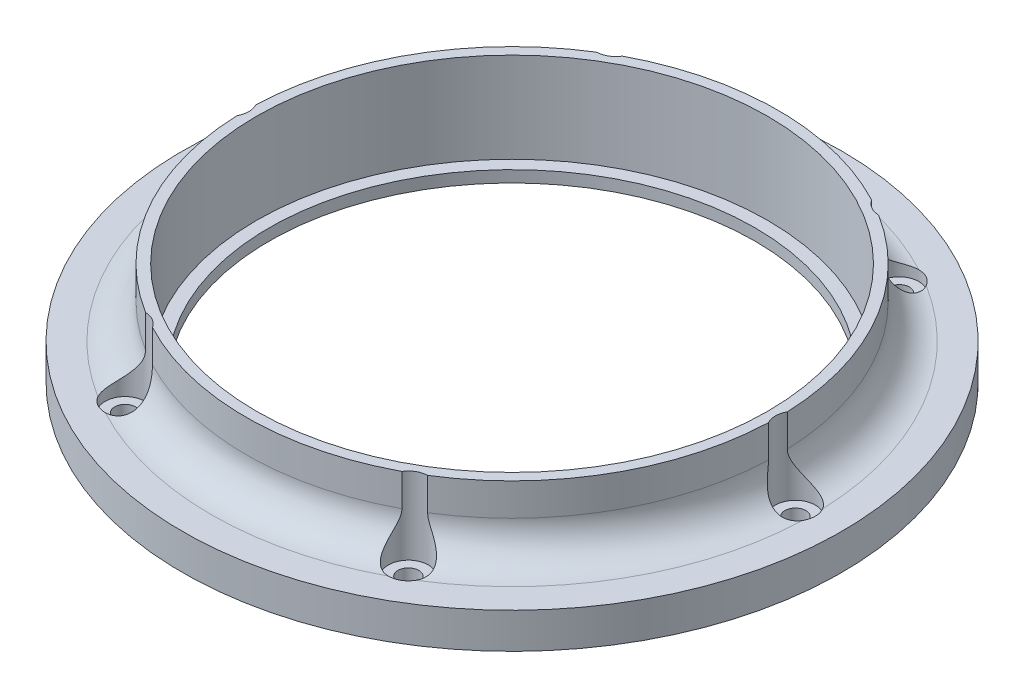
SolidWorks part; units mm, degrees
ref_plane "Front Plane" through (0, 0, 0) normal (0, 0, 1) x (1, 0, 0)
ref_plane "Top Plane" through (0, 0, 0) normal (0, 1, 0) x (1, 0, 0)
ref_plane "Right Plane" through (0, 0, 0) normal (1, 0, 0) x (0, 0, -1)
sketch "Sketch1" plane through (0, 0, 0) normal (0, 1, 0) x (1, 0, 0)
  circle A0 centre (0, 0) radius 61.25 construction
  circle A1 centre (0, 0) radius 55.25
  circle A2 centre (0, 0) radius 57.5
  dimension "D1" = 122.5
  dimension "D2" = 110.5
  dimension "D3" = 115
extrude "Boss-Extrude1" add sketch "Sketch1" along normal blind 22
sketch "Sketch2" plane through (0, 0, 0) normal (0, -1, 0) x (1, 0, 0)
  circle A0 centre (0, 0) radius 61.25 construction
  circle A1 centre (0, 0) radius 71.25
  circle A2 centre (0, 0) radius 57.5 construction
  circle A3 centre (0, 0) radius 57.5
  dimension "D1" = 122.5
  dimension "D2" = 10
extrude "Boss-Extrude2" add sketch "Sketch2" against normal blind 7.5
hole_wizard "CBORE for M4 SBHCS1" positions "Sketch6" profile "Sketch5" counterbore size "M4" standard "ANSI Metric" end condition through all
sketch "Sketch6" plane through (0, 7.5, 0) normal (0, 1, 0) x (1, 0, 0)
  circle A0 centre (0, 0) radius 61.25 construction
  point P0 (-61.25, 0)
  dimension "D1" = 122.5
sketch "Sketch5" plane through (-61.25, 7.5, 0) normal (1, 0, 0) x (0, 0, 1)
  line L0 (0, 0) -> (0, 7.5)
  line L1 (0, 7.5) -> (2.25, 7.5)
  line L3 (2.25, 7.5) -> (2.25, 2.2)
  line L4 (2.25, 2.2) -> (4.3, 2.2)
  line L5 (4.3, 2.2) -> (4.3, 0)
  line L7 (4.3, 0) -> (0, 0)
  line L11 (0, -6.35) -> (0, 107.95) construction
  dimension "Thru Hole Dia." = 4.5
  dimension "Thru Hole Depth" = 7.5
  dimension "C'Bore Dia." = 8.6
  dimension "C'Bore Depth" = 2.2
fillet "Fillet2" radius 7.5 1 edges at (57.5, 7.5, 0)
sketch "Sketch7" plane through (0, 7.5, 0) normal (0, 1, 0) x (1, 0, 0)
  circle A1 centre (-61.25, 0) radius 4.3
  circle A2 centre (-61.25, 0) radius 4.3
  dimension "D1" = 0
extrude "Cut-Extrude1" cut sketch "Sketch7" along normal through all
pattern_circular "CirPattern1" count 6 over 360 about axis through (0, 7.5, 0) along (0, -1, 0) of "Cut-Extrude1", "CBORE for M4 SBHCS1"
sketch "Sketch8" plane through (0, 0, 0) normal (0, 1, 0) x (1, 0, 0)
  circle A0 centre (0, 0) radius 52.5
  arc A12 (-57.4639, -2.0384) -> (-30.4972, -48.746) centre (0, 0) ccw
  arc A13 (-26.9666, -50.7844) -> (-30.4972, -48.746) centre (-30.625, -53.0441) ccw
  arc A14 (-26.9666, -50.7844) -> (26.9666, -50.7844) centre (0, 0) ccw
  arc A15 (30.4972, -48.746) -> (26.9666, -50.7844) centre (30.625, -53.0441) ccw
  arc A16 (30.4972, -48.746) -> (57.4639, -2.0384) centre (0, 0) ccw
  arc A17 (57.4639, 2.0384) -> (57.4639, -2.0384) centre (61.25, 0) ccw
  arc A18 (57.4639, 2.0384) -> (30.4972, 48.746) centre (0, 0) ccw
  arc A19 (26.9666, 50.7844) -> (30.4972, 48.746) centre (30.625, 53.0441) ccw
  arc A20 (26.9666, 50.7844) -> (-26.9666, 50.7844) centre (0, 0) ccw
  arc A21 (-30.4972, 48.746) -> (-26.9666, 50.7844) centre (-30.625, 53.0441) ccw
  arc A22 (-30.4972, 48.746) -> (-57.4639, 2.0384) centre (0, 0) ccw
  arc A23 (-57.4639, -2.0384) -> (-57.4639, 2.0384) centre (-61.25, 0) ccw
  arc A24 (-57.4639, -2.0384) -> (-30.4972, -48.746) centre (0, 0) ccw
  arc A25 (-26.9666, -50.7844) -> (-30.4972, -48.746) centre (-30.625, -53.0441) ccw
  arc A26 (-26.9666, -50.7844) -> (26.9666, -50.7844) centre (0, 0) ccw
  arc A27 (30.4972, -48.746) -> (26.9666, -50.7844) centre (30.625, -53.0441) ccw
  arc A28 (30.4972, -48.746) -> (57.4639, -2.0384) centre (0, 0) ccw
  arc A29 (57.4639, 2.0384) -> (57.4639, -2.0384) centre (61.25, 0) ccw
  arc A30 (57.4639, 2.0384) -> (30.4972, 48.746) centre (0, 0) ccw
  arc A31 (26.9666, 50.7844) -> (30.4972, 48.746) centre (30.625, 53.0441) ccw
  arc A32 (26.9666, 50.7844) -> (-26.9666, 50.7844) centre (0, 0) ccw
  arc A33 (-30.4972, 48.746) -> (-26.9666, 50.7844) centre (-30.625, 53.0441) ccw
  arc A34 (-30.4972, 48.746) -> (-57.4639, 2.0384) centre (0, 0) ccw
  arc A35 (-57.4639, -2.0384) -> (-57.4639, 2.0384) centre (-61.25, 0) ccw
  dimension "D2" = 5
  dimension "D1" = 0
extrude "Boss-Extrude3" add sketch "Sketch8" along normal blind 2.5
sketch "Sketch10" plane through (0, 0, 0) normal (0, -1, 0) x (1, 0, 0)
  circle A0 centre (0, 0) radius 55.25 construction
  circle A1 centre (0, 0) radius 71.25
  circle A2 centre (0, 0) radius 71.25
  circle A3 centre (61.25, 0) radius 2.25 construction
  circle A4 centre (30.625, 53.0441) radius 2.25 construction
  circle A5 centre (-30.625, 53.0441) radius 2.25 construction
  circle A6 centre (-61.25, 0) radius 2.25 construction
  circle A7 centre (-30.625, -53.0441) radius 2.25 construction
  circle A8 centre (30.625, -53.0441) radius 2.25 construction
  circle A9 centre (0, 0) radius 55.25
  circle A10 centre (61.25, 0) radius 2.25
  circle A11 centre (30.625, 53.0441) radius 2.25
  circle A12 centre (-30.625, 53.0441) radius 2.25
  circle A13 centre (-61.25, 0) radius 2.25
  circle A14 centre (-30.625, -53.0441) radius 2.25
  circle A15 centre (30.625, -53.0441) radius 2.25
  dimension "D1" = 0
extrude "Boss-Extrude4" add sketch "Sketch10" along normal blind 0.2
